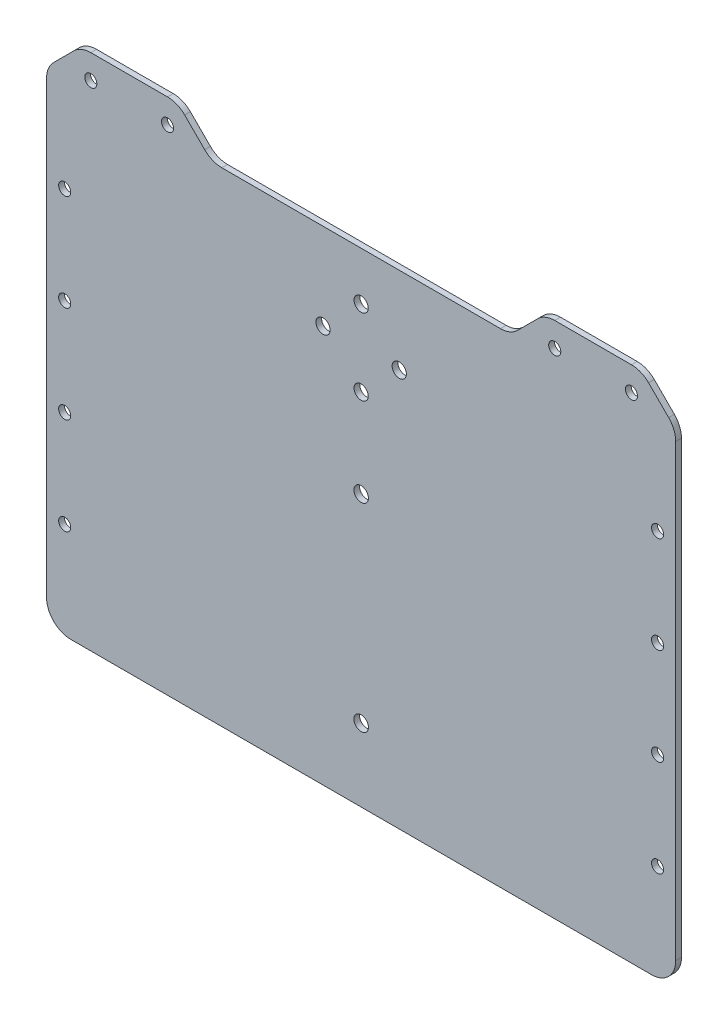
SolidWorks part; units mm, degrees
ref_plane "Front Plane" through (0, 0, 0) normal (0, 0, 1) x (1, 0, 0)
ref_plane "Top Plane" through (0, 0, 0) normal (0, 1, 0) x (1, 0, 0)
ref_plane "Right Plane" through (0, 0, 0) normal (1, 0, 0) x (0, 0, -1)
sketch "Sketch1" plane through (0, 0, 0) normal (0, 0, 1) x (1, 0, 0)
  line L0 (0, -63.5) -> (0, 63.5) construction
  line L2 (-82.55, 60.8697) -> (-82.55, -57.15)
  line L3 (-76.2, -63.5) -> (76.2, -63.5)
  line L4 (82.55, 60.8697) -> (82.55, -57.15)
  line L5 (-82.55, 63.5) -> (82.55, -63.5) construction
  line L6 (-82.55, -63.5) -> (82.55, 63.5) construction
  line L7 (-80.6901, 65.3599) -> (-75.4296, 70.6204)
  line L8 (-70.9395, 72.4803) -> (-50.8, 72.4803)
  line L9 (-46.3099, 70.6204) -> (-41.0494, 65.3599)
  line L10 (46.3099, 70.6204) -> (41.0494, 65.3599)
  line L11 (70.9395, 72.4803) -> (50.8, 72.4803)
  line L12 (80.6901, 65.3599) -> (75.4296, 70.6204)
  line L13 (-73.5697, 72.4803) -> (-82.55, 72.4803) construction
  line L14 (-82.55, 72.4803) -> (-82.55, 63.5) construction
  line L15 (-36.5592, 63.5) -> (0, 63.5)
  line L16 (0, 63.5) -> (36.5592, 63.5)
  circle A0 centre (-77.7875, -38.1) radius 1.5875
  circle A1 centre (-77.7875, -12.7) radius 1.5875
  circle A2 centre (-77.7875, 12.7) radius 1.5875
  circle A3 centre (-77.7875, 38.1) radius 1.5875
  circle A4 centre (77.7875, 38.1) radius 1.5875
  circle A5 centre (77.7875, 12.7) radius 1.5875
  circle A6 centre (77.7875, -12.7) radius 1.5875
  circle A7 centre (77.7875, -38.1) radius 1.5875
  arc A8 (82.55, 60.8697) -> (80.6901, 65.3599) centre (76.2, 60.8697) ccw
  arc A9 (75.4296, 70.6204) -> (70.9395, 72.4803) centre (70.9395, 66.1303) ccw
  arc A10 (46.3099, 70.6204) -> (50.8, 72.4803) centre (50.8, 66.1303) cw
  arc A11 (41.0494, 65.3599) -> (36.5592, 63.5) centre (36.5592, 69.85) cw
  arc A12 (-36.5592, 63.5) -> (-41.0494, 65.3599) centre (-36.5592, 69.85) cw
  arc A13 (-46.3099, 70.6204) -> (-50.8, 72.4803) centre (-50.8, 66.1303) ccw
  arc A14 (-70.9395, 72.4803) -> (-75.4296, 70.6204) centre (-70.9395, 66.1303) ccw
  arc A15 (-82.55, 60.8697) -> (-80.6901, 65.3599) centre (-76.2, 60.8697) cw
  arc A16 (76.2, -63.5) -> (82.55, -57.15) centre (76.2, -57.15) ccw
  arc A17 (-76.2, -63.5) -> (-82.55, -57.15) centre (-76.2, -57.15) cw
  circle A18 centre (-70.9395, 66.1303) radius 1.5875
  circle A19 centre (-50.8, 66.1303) radius 1.5875
  circle A20 centre (50.8, 66.1303) radius 1.5875
  circle A21 centre (70.9395, 66.1303) radius 1.5875
  point P0 (0, 0)
  point P36 (73.5697, 72.4803)
  point P39 (48.1697, 72.4803)
  point P42 (39.1895, 63.5)
  point P45 (-39.1895, 63.5)
  point P48 (-48.1697, 72.4803)
  dimension "D3" = 3.175
  dimension "D11" = 6.35
  dimension "D12" = 6.35
  dimension "D13" = 3.175
  dimension "D14" = 3.175
  dimension "D1" = 165.1
  dimension "D2" = 127
  dimension "D4" = 25.4
  dimension "D5" = 4.7625
  dimension "D7" = 50.8
  dimension "D8" = 12.7
  dimension "D9" = 135
  dimension "D10" = 25.4
  dimension "D6" = 4
extrude "Boss-Extrude1" add sketch "Sketch1" along normal blind 1.5
sketch "Sketch2" plane through (0, 0, 1.5) normal (0, 0, 1) x (1, 0, 0)
  line L0 (0, -44.45) -> (0, 7.6334) construction
  line L1 (0, -63.5) -> (0, 63.5) construction
  line L3 (-82.55, 1.8599) -> (82.55, 1.8599) construction
  line L4 (-82.55, 60.8697) -> (-82.55, -57.15) construction
  line L5 (82.55, -57.15) -> (82.55, 60.8697) construction
  line L7 (-76.2, -63.5) -> (76.2, -63.5) construction
  circle A0 centre (0, -44.45) radius 1.9062
  circle A1 centre (0, 7.6334) radius 1.9062
  dimension "D2" = 3.8125
  dimension "D3" = 3.8125
  dimension "D1" = 52.0834
  dimension "D4" = 19.05
extrude "Cut-Extrude1" cut sketch "Sketch2" against normal through all
sketch "Sketch3" plane through (0, 0, 1.5) normal (0, 0, 1) x (1, 0, 0)
  line L0 (0, 50.8) -> (0, 30.8) construction
  line L1 (-10, 40.8) -> (10, 40.8) construction
  line L2 (-10, 40.8) -> (0, 50.8) construction
  line L3 (0, 50.8) -> (10, 40.8) construction
  line L4 (10, 40.8) -> (0, 30.8) construction
  line L5 (0, 30.8) -> (-10, 40.8) construction
  line L6 (0, 63.5) -> (0, -63.5) construction
  line L8 (-76.2, -63.5) -> (76.2, -63.5) construction
  circle A0 centre (0, 50.8) radius 1.8669
  circle A1 centre (-10, 40.8) radius 1.8669
  circle A2 centre (0, 30.8) radius 1.8669
  circle A3 centre (10, 40.8) radius 1.8669
  dimension "D1" = 3.7338
  dimension "D2" = 12.7
extrude "Cut-Extrude2" cut sketch "Sketch3" against normal through all
equation "\"Top Plate Width\" = 5in"
equation "\"Plate Width\" = 5in"
equation "\"Plate Thickness\" = 0.375in"
equation "\"Num holes\" = 4"
equation "\"Plate Height\" = 1.25in"
equation "\"D2@Sketch1\"=\"Plate Width\""
equation "\"Plate Clearance Hole Diameter\" = 0.125in"
equation "\"D3@Sketch1\"=\"Plate Clearance Hole Diameter\""
equation "\"Hole Spacing\"= \"Plate Width\" / ( \"Num holes\" + 1 )"
equation "\"D5@Sketch1\"=\"Plate Thickness\" / 2"
equation "\"D4@Sketch1\"=\"Hole Spacing\""
equation "\"D7@Sketch1\"= 2 * \"Hole Spacing\""
equation "\"D13@Sketch1\"=\"Plate Clearance Hole Diameter\""
equation "\"D14@Sketch1\"=\"Plate Clearance Hole Diameter\""
